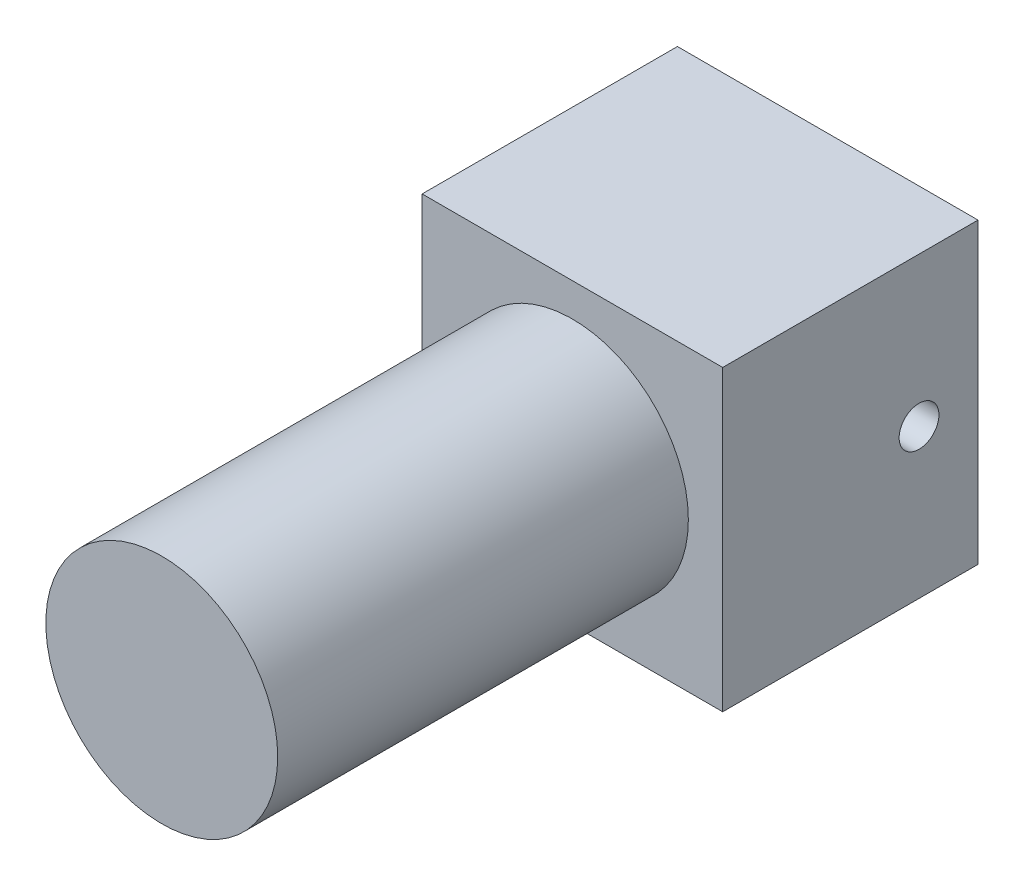
SolidWorks part; units mm, degrees
ref_plane "Front Plane" through (0, 0, 0) normal (0, 0, 1) x (1, 0, 0)
ref_plane "Top Plane" through (0, 0, 0) normal (0, 1, 0) x (1, 0, 0)
ref_plane "Right Plane" through (0, 0, 0) normal (1, 0, 0) x (0, 0, -1)
sketch "Sketch1" plane through (0, 0, 0) normal (0, 0, 1) x (1, 0, 0)
  line L1 (-19.25, -19.1) -> (19.25, -19.1)
  line L2 (-19.25, -19.1) -> (-19.25, 19.1)
  line L3 (-19.25, 19.1) -> (19.25, 19.1)
  line L4 (19.25, -19.1) -> (19.25, 19.1)
  line L5 (-19.25, -19.1) -> (19.25, 19.1) construction
  line L6 (-19.25, 19.1) -> (19.25, -19.1) construction
  point P0 (0, 0)
  dimension "D1" = 38.5
  dimension "D2" = 38.2
extrude "Boss-Extrude1" add sketch "Sketch1" along normal blind 32.7
sketch "Sketch2" plane through (0, 0, 32.7) normal (0, 0, 1) x (1, 0, 0)
  circle A0 centre (0, 0) radius 14.85
  dimension "D1" = 29.7
extrude "Boss-Extrude2" add sketch "Sketch2" along normal blind 52.6
sketch "Sketch3" plane through (19.25, 0, 0) normal (1, 0, 0) x (0, 0, -1)
  circle A0 centre (-7.5543, 0) radius 2.55
  dimension "D1" = 5.1
extrude "Cut-Extrude1" cut sketch "Sketch3" against normal blind 7.2136 contours A0
mirror "Mirror1" about plane through (0, 0, 0) normal (1, 0, 0) of "Cut-Extrude1"
sketch "Sketch4" plane through (0, 0, 0) normal (0, 0, -1) x (-1, 0, 0)
  circle A0 centre (0, -16.6516) radius 2.066
extrude "Boss-Extrude3" add sketch "Sketch4" along normal blind 5.08
